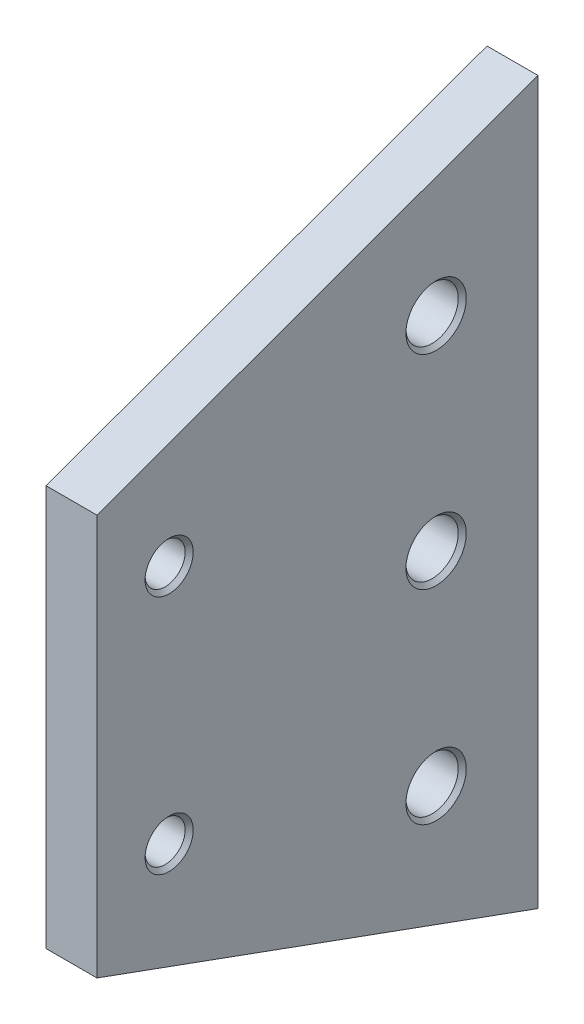
SolidWorks part; units mm, degrees
material "6061 Alloy"
ref_plane "Front Plane" through (0, 0, 0) normal (0, 0, 1) x (1, 0, 0)
ref_plane "Top Plane" through (0, 0, 0) normal (0, 1, 0) x (1, 0, 0)
ref_plane "Right Plane" through (0, 0, 0) normal (1, 0, 0) x (0, 0, -1)
sketch "Sketch1" plane through (0, 0, 0) normal (1, 0, 0) x (0, 0, -1)
  line L0 (-27.5, 0) -> (27.5, 0) construction
  line L1 (-27.5, 25) -> (-27.5, -25)
  line L3 (27.5, 45) -> (27.5, -45)
  line L4 (-27.5, 25) -> (27.5, 45)
  line L5 (-27.5, -25) -> (27.5, -45)
  dimension "D1" = 50
  dimension "D4" = 55
  dimension "D5" = 90
extrude "1/4 Inch Sheet" add sketch "Sketch1" along normal mid plane 6.35
sketch "Sketch2" plane through (0, 0, 0) normal (1, 0, 0) x (0, 0, -1)
  line L0 (-27.5, 0) -> (27.5, 0) construction
  line L1 (-27.5, 25) -> (-27.5, -25) construction
  line L2 (27.5, -45) -> (27.5, 45) construction
  line L3 (-18.5, 15) -> (-18.5, -15) construction
  line L4 (15, -25.4) -> (15, 25.4) construction
  circle A0 centre (-18.5, 15) radius 2.5
  circle A1 centre (-18.5, -15) radius 2.5
  point P10 (-18.5, 0)
  point P12 (15, 0)
  dimension "D5" = 5
  dimension "D1" = 30
  dimension "D2" = 25.4
  dimension "D3" = 9
  dimension "D4" = 12.5
extrude "Cut-Extrude1 M5" cut sketch "Sketch2" against normal through all both and the other way through all
hole_wizard "1/4 in Clearance Hole1" positions "Sketch3" profile "Sketch4" hole size "1/4" standard "ANSI Inch" end condition up to next
sketch "Sketch3" plane through (3.175, 0, 0) normal (1, 0, 0) x (0, 0, -1)
  line L0 (0, 0) -> (14.8, 0) construction
  line L1 (14.8, 0) -> (14.8, 25.4) construction
  line L2 (14.8, 0) -> (14.8, -25.4) construction
  line L4 (27.5, -45) -> (27.5, 45) construction
  point P0 (14.8, 25.4)
  point P2 (14.8, 0)
  point P4 (14.8, -25.4)
  dimension "D2" = 25.4
  dimension "D1" = 12.7
sketch "Sketch4" plane through (3.175, 25.4, -14.8) normal (0, 1, 0) x (0, 0, -1)
  line L0 (0, 0) -> (0, 6.35)
  line L1 (0, 6.35) -> (3.2639, 6.35)
  line L2 (3.2639, 6.35) -> (3.2639, 0)
  line L5 (3.2639, 0) -> (0, 0)
  line L11 (0, -6.35) -> (0, 107.95) construction
  dimension "Thru Hole Dia." = 6.5278
  dimension "Thru Hole Depth" = 6.35
chamfer "Chamfer1" distance 0.5 angle 45 10 edges at (-3.175, -25.4, -11.5361) (3.175, -25.4, -18.0639) (3.175, -15, 16) (-3.175, -15, 16) (3.175, 15, 16) (-3.175, 15, 16) (-3.175, 0, -11.5361) (3.175, 0, -18.0639) (-3.175, 25.4, -11.5361) (3.175, 25.4, -18.0639)
equation "\"D2@Sketch2\"=1in"
equation "\"D1@Sketch3\"=25.4/2"
